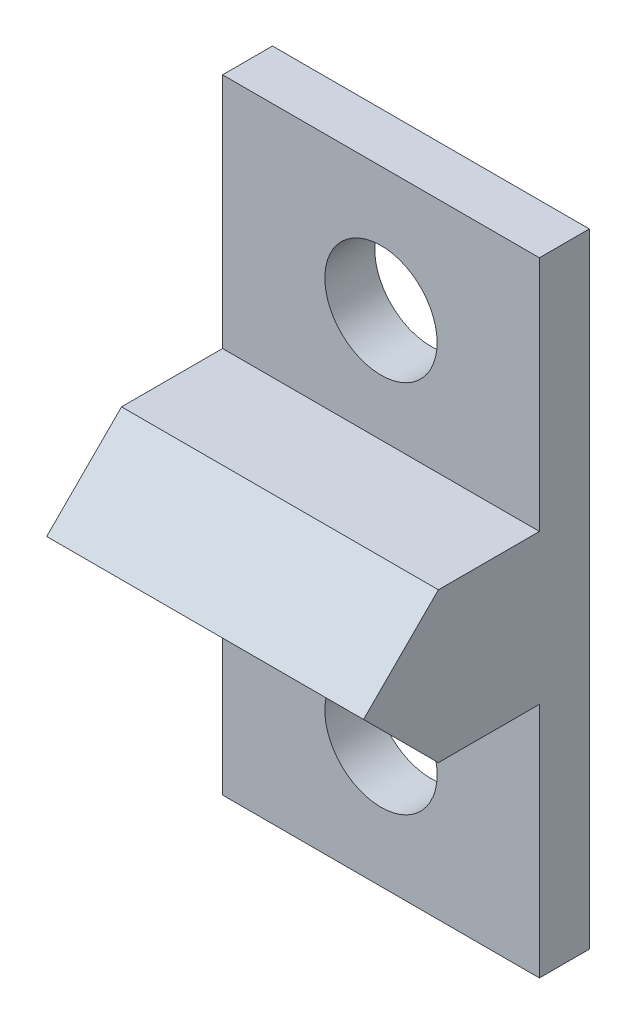
SolidWorks part; units mm, degrees
ref_plane "Front Plane" through (0, 0, 0) normal (0, 0, 1) x (1, 0, 0)
ref_plane "Top Plane" through (0, 0, 0) normal (0, 1, 0) x (1, 0, 0)
ref_plane "Right Plane" through (0, 0, 0) normal (1, 0, 0) x (0, 0, -1)
sketch "Sketch2" plane through (0, 0, 0) normal (0, 0, 1) x (1, 0, 0)
  line L0 (0, 20) -> (0, 5)
  line L2 (-6.35, 0) -> (6.35, 0)
  line L3 (-6.35, 0) -> (-6.35, 25)
  line L4 (-6.35, 25) -> (6.35, 25)
  line L5 (6.35, 0) -> (6.35, 25)
  circle A0 centre (0, 5) radius 2.25
  circle A1 centre (0, 20) radius 2.25
  dimension "D1" = 4.5
  dimension "D2" = 4.5
  dimension "D3" = 15
  dimension "D4" = 0
  dimension "D5" = 5
  dimension "D6" = 6.35
  dimension "D7" = 12.7
  dimension "D8" = 25
  dimension "D9" = 5
extrude "Boss-Extrude1" add sketch "Sketch2" along normal blind 2 contours L2 L5 L4 L3 A1 A0 region at (-6.0696, 12.5, 0)
sketch "Sketch3" plane through (0, 0, 2) normal (0, 0, 1) x (1, 0, 0)
  line L0 (-6.35, 0) -> (-6.35, 25) construction
  line L1 (-6.35, 9.5) -> (6.35, 9.5)
  line L2 (-6.35, 9.5) -> (-6.35, 15.5)
  line L3 (-6.35, 15.5) -> (6.35, 15.5)
  line L4 (6.35, 9.5) -> (6.35, 15.5)
  line L5 (6.35, 0) -> (6.35, 25) construction
  circle A0 centre (0, 5) radius 2.25 construction
  circle A1 centre (0, 20) radius 2.25 construction
  dimension "D1" = 4.5
  dimension "D2" = 4.5
extrude "Boss-Extrude2" add sketch "Sketch3" along normal blind 7.05
chamfer "Chamfer1" distance 3 angle 45 2 edges at (0, 9.5, 9.05) (0, 15.5, 9.05)
